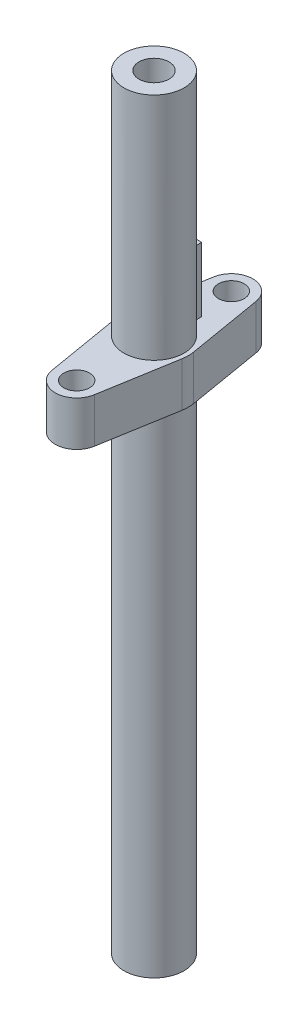
SolidWorks part; units mm, degrees
note: The reader was unsure of these and kept them because the rebuilt part matched: shared geometry of "Sketch2<2>".
ref_plane "Ön Düzlem" through (0, 0, 0) normal (0, 0, 1) x (1, 0, 0)
ref_plane "Üst Düzlem" through (0, 0, 0) normal (0, 1, 0) x (1, 0, 0)
ref_plane "Sağ Düzlem" through (0, 0, 0) normal (1, 0, 0) x (0, 0, -1)
sketch "Sketch1" plane through (0, 0, 0) normal (0, 1, 0) x (1, 0, 0)
  circle A0 centre (0, 0) radius 3.5
  dimension "D1" = 7
extrude "Boss-Extrude1" add sketch "Sketch1" along normal blind 87.927
sketch "Sketch2" plane through (0, 0, 0) normal (0, -1, 0) x (1, 0, 0)
  circle A0 centre (0, 0) radius 1.75
  dimension "D1" = 3.5
extrude "Cut-Extrude1" cut sketch "Sketch2" against normal blind 8.9
extrude "Cut-Extrude2" cut sketch "Sketch2<2>" along normal blind 8.9 from surface at -87.927 starting at face at (0, 87.927, 3.5)
sketch "Sketch2<2>" plane through (0, 0, 0) normal (0, -1, 0) x (1, 0, 0) same geometry as "Sketch2"
ref_plane "Plane1" through (-3.5, 0, 0) normal (-1, 0, 0) x (0, 0, 1)
sketch "Sketch3" plane through (-3.5, 0, 0) normal (-1, 0, 0) x (0, 0, 1)
  line L0 (0, 4.677) -> (0, 0) construction
  line L1 (3.5, 87.927) -> (-3.5, 87.927) construction
  circle A0 centre (0, 4.677) radius 1.75
  circle A1 centre (0, 82.177) radius 1.75
  dimension "D2" = 3.5
  dimension "D1" = 4.677
  dimension "D3" = 5.75
extrude "Cut-Extrude3" cut sketch "Sketch3" against normal up to surface (3.5 mm away) up to face at (0, 79.027, 1.75)
ref_plane "Plane2" through (0, 68.677, 0) normal (0, 1, 0) x (1, 0, 0)
sketch "Sketch4" plane through (0, 68.677, 0) normal (0, 1, 0) x (1, 0, 0)
  line L0 (-1, 3.3541) -> (-1, 4.8541) construction
  line L1 (1, 3.3541) -> (1, 4.8541) construction
  line L2 (-1, 4.1041) -> (1, 4.1041) construction
  line L3 (-1, 4.8541) -> (1, 4.8541) construction
  line L4 (0.85, 3.2404) -> (0.85, 4.7041)
  line L5 (-0.85, 4.7041) -> (0.85, 4.7041)
  line L6 (-0.85, 3.2404) -> (-0.85, 4.7041)
  arc A0 (-1, 3.3541) -> (1, 3.3541) centre (0, 0) ccw construction
  arc A1 (-0.85, 3.2404) -> (0.85, 3.2404) centre (0, 0) ccw
  circle A2 centre (0, 0) radius 3.5 construction
  arc A3 (-0.85, 3.3952) -> (0.85, 3.3952) centre (0, 0) ccw construction
  point P9 (0, 4.1041)
  dimension "D1" = 7
  dimension "D2" = 2
  dimension "D3" = 1.5
  dimension "D4" = 0.15
extrude "Boss-Extrude2" add sketch "Sketch4" against normal blind 7.5
sketch "Sketch5" plane through (0, 61.177, 0) normal (0, -1, 0) x (1, 0, 0)
  line L0 (-3.9441, 0.6667) -> (-2.465, 9.4167)
  line L1 (2.465, 9.4167) -> (3.9441, 0.6667)
  line L2 (4, 0) -> (-4, 0) construction
  line L3 (2.465, -9.4167) -> (3.9441, -0.6667)
  line L4 (-3.9441, -0.6667) -> (-2.465, -9.4167)
  arc A0 (2.465, 9.4167) -> (-2.465, 9.4167) centre (0, 9) ccw
  arc A1 (-3.9441, 0.6667) -> (-3.9441, -0.6667) centre (0, 0) ccw
  circle A2 centre (0, 9) radius 1.5
  circle A3 centre (0, 0) radius 3.5 construction
  circle A4 centre (0, 0) radius 3.5
  arc A5 (2.465, -9.4167) -> (-2.465, -9.4167) centre (0, -9) cw
  circle A6 centre (0, -9) radius 1.5
  arc A7 (3.9441, -0.6667) -> (3.9441, 0.6667) centre (0, 0) ccw
  point P13 (0, 0)
  dimension "D1" = 5
  dimension "D3" = 8
  dimension "D4" = 3
  dimension "D2" = 9
extrude "Boss-Extrude3" add sketch "Sketch5" along normal blind 5.2
sketch "Sketch6" plane through (0, 0, 0) normal (0, 1, 0) x (1, 0, 0)
  circle A0 centre (0, 0) radius 3.5
  circle A1 centre (0, 0) radius 3.5
  circle A2 centre (0, 0) radius 3.5 construction
  circle M5 centre (0, 0) radius 1.75
  circle M6 centre (0, 0) radius 3.5
extrude "Boss-Extrude5" add sketch "Sketch6" against normal blind 1.1 contours M6 M5
sketch "Sketch7" plane through (0, 79.027, 0) normal (0, 1, 0) x (1, 0, 0)
  circle A1 centre (0, 0) radius 1.75
  circle A2 centre (0, 0) radius 1.75
  dimension "D1" = 0
extrude "Boss-Extrude6" add sketch "Sketch7" along normal blind 0.4
sketch "Sketch8" plane through (0, 8.9, 0) normal (0, -1, 0) x (1, 0, 0)
  circle A1 centre (0, 0) radius 1.75
  circle A2 centre (0, 0) radius 1.75
  dimension "D1" = 0
extrude "Boss-Extrude7" add sketch "Sketch8" along normal blind 1.473
